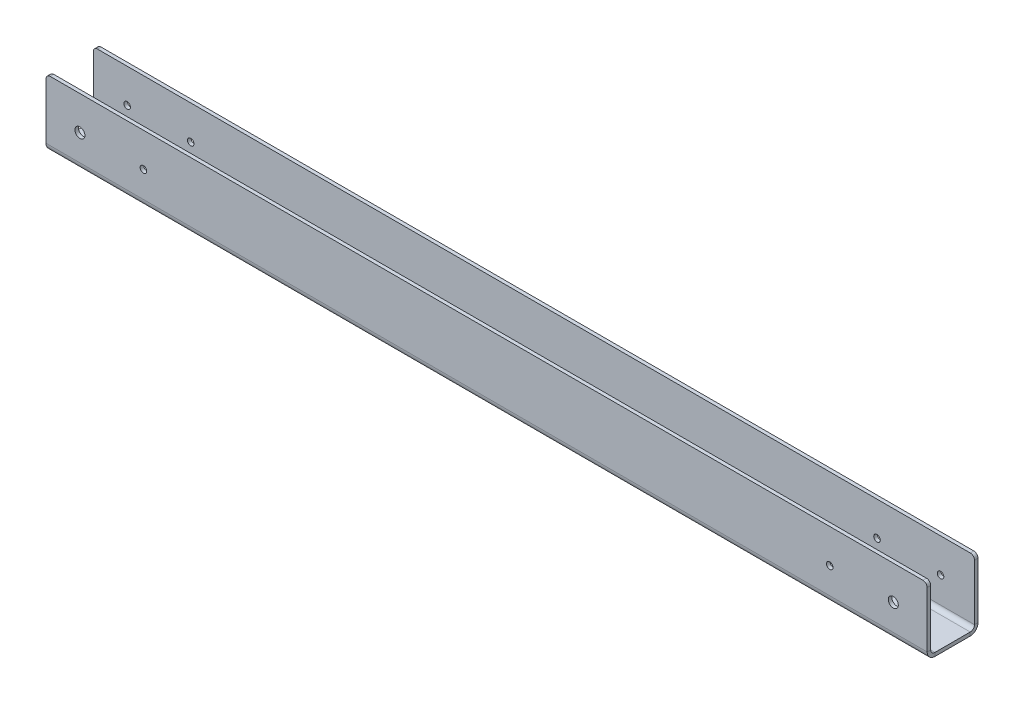
SolidWorks part; units mm, degrees
note: The reader was unsure of these and kept them because the rebuilt part matched: flange length of "Edge-Flange1".
material "Plain Carbon Steel"
ref_plane "Front Plane" through (0, 0, 0) normal (0, 0, 1) x (1, 0, 0)
ref_plane "Top Plane" through (0, 0, 0) normal (0, 1, 0) x (1, 0, 0)
ref_plane "Right Plane" through (0, 0, 0) normal (1, 0, 0) x (0, 0, -1)
sketch "Sketch1" plane through (0, 0, 0) normal (0, 1, 0) x (1, 0, 0)
  line L1 (45.72, -3.175) -> (706.12, -3.175)
  line L3 (45.72, 34.925) -> (706.12, 34.925)
  line L6 (45.72, 34.925) -> (45.72, -3.175)
  line L13 (706.12, 34.925) -> (706.12, -3.175)
  dimension "D1" = 660.4
  dimension "D2" = 38.1
base flange "Base-Flange1" sketch "Sketch1" thickness 2.6568 reverse thickness direction no parameters "D1"=3.175
edge flange "Edge-Flange1" sketch "Sketch10" flange profiles "Sketch10", "Sketch11" flange angle 90 flange length 50.8 flange position material inside bend radius 3.175 thickness 2.6568 relief rectangular parameters "D6"=10, "D8"=1
sketch "Sketch10" plane through (0, 0, 3.175) normal (0, 0, -1) x (-1, 0, 0)
  line L2 (-706.12, 0) -> (-706.12, 48.1432)
  line L3 (-706.12, 48.1432) -> (-45.72, 48.1432)
  line L4 (-45.72, 48.1432) -> (-45.72, 0)
  line L5 (-45.72, 0) -> (-706.12, 0) construction
  line L6 (-45.72, 0) -> (-706.12, 0)
sketch "Sketch11" plane through (0, 0, -34.925) normal (0, 0, 1) x (1, 0, 0)
  line L0 (706.12, 0) -> (45.72, 0) construction
  line L1 (706.12, 0) -> (45.72, 0)
  line L2 (706.12, 0) -> (706.12, 48.1432)
  line L3 (706.12, 48.1432) -> (45.72, 48.1432)
  line L4 (45.72, 48.1432) -> (45.72, 0)
bend "EdgeBend1" bend radius 3.175 bend angle 90 parameters "D5"=1
bend "EdgeBend2" bend radius 3.175 bend angle 90 parameters "D5"=2
edge flange "Edge-Flange2" [suppressed] sketch "Sketch20" flange profiles "Sketch20", "Sketch21", "Sketch22", "Sketch23" flange angle 90 flange position material inside bend radius 3.175 thickness 2.6568
sketch "Sketch20" plane through (0, 0, 0) normal (0, 0, -1) x (-1, 0, 0)
  line L2 (-749.3, 0) -> (-749.3, 48.1432)
  line L3 (-749.3, 48.1432) -> (-704.9084, 48.1432)
  line L4 (-704.9084, 48.1432) -> (-704.9084, 0)
  line L9 (-704.9084, 0) -> (-749.3, 0) construction
  line L10 (-704.9084, 0) -> (-749.3, 0)
sketch "Sketch21" plane through (0, 0, -31.75) normal (0, 0, 1) x (1, 0, 0)
  line L2 (749.3, 0) -> (749.3, 48.1432)
  line L3 (749.3, 48.1432) -> (704.9084, 48.1432)
  line L4 (704.9084, 48.1432) -> (704.9084, 0)
  line L7 (749.3, 0) -> (704.9084, 0) construction
  line L8 (749.3, 0) -> (704.9084, 0)
sketch "Sketch22" plane through (0, 0, -31.75) normal (0, 0, 1) x (1, 0, 0)
  line L0 (44.3916, 0) -> (0, 0) construction
  line L1 (44.3916, 0) -> (0, 0)
  line L2 (44.3916, 0) -> (44.3916, 48.1432)
  line L3 (44.3916, 48.1432) -> (0, 48.1432)
  line L4 (0, 48.1432) -> (0, 0)
sketch "Sketch23" plane through (0, 0, 0) normal (0, 0, -1) x (-1, 0, 0)
  line L0 (0, 0) -> (-44.3916, 0) construction
  line L1 (0, 0) -> (-44.3916, 0)
  line L2 (0, 0) -> (0, 48.1432)
  line L3 (0, 48.1432) -> (-44.3916, 48.1432)
  line L4 (-44.3916, 48.1432) -> (-44.3916, 0)
bend "EdgeBend3" bend radius 3.175 bend angle 90 parameters "D5"=3
bend "EdgeBend4" bend radius 3.175 bend angle 90 parameters "D5"=4
bend "EdgeBend5" bend radius 3.175 bend angle 90 parameters "D5"=5
bend "EdgeBend6" bend radius 3.175 bend angle 90 parameters "D5"=6, "D6"=10, "D7"=50.8
hole_wizard "#10 (0.1935) Diameter Hole1" [suppressed] positions "Sketch24" profile "Sketch25" hole size "#10" standard "ANSI Inch"
sketch "Sketch24" [suppressed] plane through (0, 0, 0) normal (0, 0, 1) x (1, 0, 0)
  line L0 (704.9084, 48.1432) -> (749.3, 48.1432) construction
  line L1 (749.3, 48.1432) -> (749.3, 3.175) construction
  line L2 (0, 3.175) -> (0, 48.1432) construction
  point P0 (739.775, 22.7432)
  point P2 (714.375, 22.7432)
  point P4 (34.925, 22.7432)
  point P6 (9.525, 22.7432)
  dimension "D1" = 25.4
  dimension "D2" = 25.4
  dimension "D3" = 9.525
  dimension "D4" = 25.4
  dimension "D5" = 9.525
sketch "Sketch25" plane through (739.775, 22.7432, 0) normal (1, 0, 0) x (0, -1, 0)
  line L0 (0, 0) -> (0, 34.925)
  line L1 (0, 34.925) -> (2.4574, 34.925)
  line L2 (2.4574, 34.925) -> (2.4574, 0)
  line L5 (2.4574, 0) -> (0, 0)
  line L11 (0, -6.35) -> (0, 107.95) construction
  dimension "Thru Hole Dia." = 4.9149
  dimension "Thru Hole Depth" = 34.925
edge flange "Edge-Flange3" [suppressed] sketch "Sketch28" flange angle 90 flange position material inside bend radius 3.175 thickness 2.6568
sketch "Sketch28" plane through (0, 48.1432, 0.5182) normal (0, 1, 0) x (1, 0, 0)
  line L0 (45.72, 0) -> (703.58, 0) construction
  line L1 (45.72, 0) -> (703.58, 0)
  line L2 (45.72, 0) -> (45.72, 12.7)
  line L3 (45.72, 12.7) -> (703.58, 12.7)
  line L4 (703.58, 12.7) -> (703.58, 0)
  dimension "D1" = 12.7
bend "EdgeBend7" bend radius 3.175 bend angle 90 parameters "D5"=7, "D6"=10, "D7"=15.3568
edge flange "Edge-Flange4" [suppressed] sketch "Sketch31" flange angle 90 flange position material inside bend radius 3.175 thickness 2.6568
sketch "Sketch31" plane through (0, 48.1432, -32.2682) normal (0, -1, 0) x (1, 0, 0)
  line L2 (45.72, 0) -> (45.72, 12.7)
  line L3 (45.72, 12.7) -> (703.58, 12.7)
  line L4 (703.58, 12.7) -> (703.58, 0)
  line L5 (703.58, 0) -> (45.72, 0) construction
  line L6 (703.58, 0) -> (45.72, 0)
  dimension "D1" = 12.7
bend "EdgeBend8" bend radius 3.175 bend angle 90 parameters "D5"=8, "D6"=10, "D7"=15.3568
hole_wizard "#10 (0.1935) Diameter Hole2" positions "Sketch32" profile "Sketch33" hole size "#10" standard "ANSI Inch" end condition up to next
sketch "Sketch32" plane through (0, 0, -34.925) normal (0, 0, -1) x (-1, 0, 0)
  line L0 (-45.72, 3.175) -> (-45.72, 48.1432) construction
  line L1 (-706.12, 48.1432) -> (-706.12, 3.175) construction
  line L2 (-45.72, 48.1432) -> (-706.12, 48.1432) construction
  point P0 (-680.72, 22.7432)
  point P2 (-633.095, 22.7432)
  point P4 (-118.745, 22.7432)
  point P6 (-71.12, 22.7432)
  dimension "D1" = 25.4
  dimension "D2" = 47.625
  dimension "D3" = 25.4
  dimension "D4" = 47.625
  dimension "D5" = 25.4
sketch "Sketch33" plane through (680.72, 22.7432, -34.925) normal (1, 0, 0) x (0, 1, 0)
  line L0 (0, 0) -> (0, 2.6568)
  line L1 (0, 2.6568) -> (2.4574, 2.6568)
  line L2 (2.4574, 2.6568) -> (2.4574, 0)
  line L5 (2.4574, 0) -> (0, 0)
  line L11 (0, -6.35) -> (0, 107.95) construction
  dimension "Thru Hole Dia." = 4.9149
  dimension "Thru Hole Depth" = 2.6568
fillet "Fillet1" radius 3.175 4 edges at (706.12, 48.1432, -33.5966) (706.12, 48.1432, 1.8466) (45.72, 48.1432, -33.5966) (45.72, 48.1432, 1.8466)
hole_wizard "#10 (0.1935) Diameter Hole3" positions "Sketch34" profile "Sketch35" hole size "#10" standard "ANSI Inch" end condition up to next
sketch "Sketch34" plane through (0, 0, 3.175) normal (0, 0, 1) x (1, 0, 0)
  line L0 (45.72, 24.0716) -> (706.12, 24.0716) construction
  line L1 (45.72, 3.175) -> (45.72, 44.9682) construction
  line L2 (706.12, 44.9682) -> (706.12, 3.175) construction
  circle A0 centre (118.745, 22.7432) radius 2.4574 construction
  circle A1 centre (633.095, 22.7432) radius 2.4574 construction
  point P9 (118.745, 22.7432)
  point P15 (633.095, 22.7432)
sketch "Sketch35" plane through (633.095, 22.7432, 3.175) normal (1, 0, 0) x (0, -1, 0)
  line L0 (0, 0) -> (0, 2.6568)
  line L1 (0, 2.6568) -> (2.4574, 2.6568)
  line L2 (2.4574, 2.6568) -> (2.4574, 0)
  line L5 (2.4574, 0) -> (0, 0)
  line L11 (0, -6.35) -> (0, 107.95) construction
  dimension "Thru Hole Dia." = 4.9149
  dimension "Thru Hole Depth" = 2.6568
hole_wizard "19/64 (0.29688) Diameter Hole1" positions "Sketch36" profile "Sketch37" hole size "19/64" standard "ANSI Inch" end condition up to next
sketch "Sketch36" plane through (0, 0, 3.175) normal (0, 0, 1) x (1, 0, 0)
  circle A0 centre (71.12, 22.7432) radius 2.4574 construction
  circle A1 centre (680.72, 22.7432) radius 2.4574 construction
  point P0 (71.12, 22.7432)
  point P5 (680.72, 22.7432)
sketch "Sketch37" plane through (71.12, 22.7432, 3.175) normal (1, 0, 0) x (0, -1, 0)
  line L0 (0, 0) -> (0, 2.6568)
  line L1 (0, 2.6568) -> (3.7704, 2.6568)
  line L2 (3.7704, 2.6568) -> (3.7704, 0)
  line L5 (3.7704, 0) -> (0, 0)
  line L11 (0, -6.35) -> (0, 107.95) construction
  dimension "Thru Hole Dia." = 7.5408
  dimension "Thru Hole Depth" = 2.6568
sketch "Bend-Lines1" [suppressed] plane through (0, 0, 0) normal (0, 1, 0) x (1, 0, 0)
sketch "Bounding-Box1" [suppressed] plane through (0, 0, 0) normal (0, 1, 0) x (1, 0, 0)
sheet metal parameters "Sheet-Metal1" thickness 2.6568 parameters "D1"=3.175
flat pattern "Flat-Pattern1" [suppressed]
sketch "Bend-Lines2" plane through (0, 0, 0) normal (0, 1, 0) x (1, 0, 0)
sketch3d "Bounding-Box2" [suppressed]
  line L0 (749.3, 38.1, 0) -> (0, 38.1, 0) construction
  line L1 (749.3, 0, 0) -> (0, 0, 0) construction
  line L2 (749.3, 38.1, 0) -> (749.3, 0, 0) construction
  line L3 (0, 38.1, 0) -> (0, 0, 0) construction
sheet metal parameters "Sheet-Metal2" thickness 2.6568 parameters "D1"=3.175
flat pattern "Flat-Pattern1"
sketch "Bend-Lines2" plane through (0, 0, 0) normal (0, 1, 0) x (1, 0, 0)
  line L0 (706.12, 32.6301) -> (45.72, 32.6301) construction
  line L1 (45.72, -0.8801) -> (706.12, -0.8801) construction
  line L2 (706.12, 32.6301) -> (45.72, 32.6301) construction
  line L3 (45.72, -0.8801) -> (706.12, -0.8801) construction
sketch3d "Bounding-Box2" [suppressed]
  line L0 (706.12, -49.3853, 0) -> (45.72, -49.3853, 0) construction
  line L1 (706.12, 81.1353, 0) -> (45.72, 81.1353, 0) construction
  line L2 (706.12, -49.3853, 0) -> (706.12, 81.1353, 0) construction
  line L3 (45.72, -49.3853, 0) -> (45.72, 81.1353, 0) construction
bend of the flat pattern "Flatten-<EdgeBend1>1"
bend of the flat pattern "Flatten-<EdgeBend2>1"
sheet metal parameters "Sheet-Metal3" thickness 2.6568 parameters "D1"=3.175
flat pattern "Flat-Pattern1"
sketch "Bend-Lines2" plane through (0, 0, 0) normal (0, 1, 0) x (1, 0, 0)
  line L0 (695.3183, 32.6301) -> (53.975, 32.6301) construction
  line L1 (53.975, -0.8801) -> (695.3183, -0.8801) construction
  line L2 (695.3183, 32.6301) -> (53.975, 32.6301) construction
  line L3 (53.975, -0.8801) -> (695.3183, -0.8801) construction
  line L4 (0, 2.2949) -> (52.6466, 2.2949) construction
  line L5 (0, 29.4551) -> (52.6466, 29.4551) construction
  line L6 (696.6467, 29.4551) -> (749.2933, 29.4551) construction
  line L7 (749.2933, 2.2949) -> (696.6467, 2.2949) construction
  line L8 (0, 2.2949) -> (52.6466, 2.2949) construction
  line L9 (0, 29.4551) -> (52.6466, 29.4551) construction
  line L10 (696.6467, 29.4551) -> (749.2933, 29.4551) construction
  line L11 (749.2933, 2.2949) -> (696.6467, 2.2949) construction
sketch3d "Bounding-Box2" [suppressed]
  line L0 (749.2933, 81.1353, 0) -> (0, 81.1353, 0) construction
  line L1 (749.2933, -49.3853, 0) -> (0, -49.3853, 0) construction
  line L2 (749.2933, 81.1353, 0) -> (749.2933, -49.3853, 0) construction
  line L3 (0, 81.1353, 0) -> (0, -49.3853, 0) construction
bend of the flat pattern "Flatten-<EdgeBend1>1"
bend of the flat pattern "Flatten-<EdgeBend2>1"
bend of the flat pattern "Flatten-<EdgeBend3>1"
bend of the flat pattern "Flatten-<EdgeBend4>1"
bend of the flat pattern "Flatten-<EdgeBend5>1"
bend of the flat pattern "Flatten-<EdgeBend6>1"
sheet metal parameters "Sheet-Metal4" thickness 2.6568 parameters "D1"=3.175
flat pattern "Flat-Pattern1"
sketch "Bend-Lines2" plane through (0, 0, 0) normal (0, 1, 0) x (1, 0, 0)
  line L0 (703.58, 32.6301) -> (45.72, 32.6301) construction
  line L1 (45.72, -0.8801) -> (703.58, -0.8801) construction
  line L2 (703.58, 32.6301) -> (45.72, 32.6301) construction
  line L3 (45.72, -0.8801) -> (703.58, -0.8801) construction
  line L4 (44.3916, 2.2949) -> (0, 2.2949) construction
  line L5 (0, 29.4551) -> (44.3916, 29.4551) construction
  line L6 (749.3, 29.4551) -> (704.9084, 29.4551) construction
  line L7 (749.3, 2.2949) -> (704.9084, 2.2949) construction
  line L8 (44.3916, 2.2949) -> (0, 2.2949) construction
  line L9 (0, 29.4551) -> (44.3916, 29.4551) construction
  line L10 (749.3, 29.4551) -> (704.9084, 29.4551) construction
  line L11 (749.3, 2.2949) -> (704.9084, 2.2949) construction
sketch3d "Bounding-Box2" [suppressed]
  line L0 (749.3, 81.1353, 0) -> (0, 81.1353, 0) construction
  line L1 (749.3, -49.3853, 0) -> (0, -49.3853, 0) construction
  line L2 (749.3, 81.1353, 0) -> (749.3, -49.3853, 0) construction
  line L3 (0, 81.1353, 0) -> (0, -49.3853, 0) construction
bend of the flat pattern "Flatten-<EdgeBend1>1"
bend of the flat pattern "Flatten-<EdgeBend2>1"
bend of the flat pattern "Flatten-<EdgeBend3>1"
bend of the flat pattern "Flatten-<EdgeBend4>1"
bend of the flat pattern "Flatten-<EdgeBend5>1"
bend of the flat pattern "Flatten-<EdgeBend6>1"
sheet metal parameters "Sheet-Metal5" thickness 2.6568 parameters "D1"=3.175
flat pattern "Flat-Pattern1"
sketch "Bend-Lines2" plane through (0, 0, 0) normal (0, 1, 0) x (1, 0, 0)
  line L0 (703.58, 32.6301) -> (45.72, 32.6301) construction
  line L1 (45.72, -0.8801) -> (703.58, -0.8801) construction
  line L2 (703.58, 32.6301) -> (45.72, 32.6301) construction
  line L3 (45.72, -0.8801) -> (703.58, -0.8801) construction
  line L4 (44.3916, 2.2949) -> (0, 2.2949) construction
  line L5 (0, 29.4551) -> (44.3916, 29.4551) construction
  line L6 (749.3, 29.4551) -> (704.9084, 29.4551) construction
  line L7 (749.3, 2.2949) -> (704.9084, 2.2949) construction
  line L8 (44.3916, 2.2949) -> (0, 2.2949) construction
  line L9 (0, 29.4551) -> (44.3916, 29.4551) construction
  line L10 (749.3, 29.4551) -> (704.9084, 29.4551) construction
  line L11 (749.3, 2.2949) -> (704.9084, 2.2949) construction
  line L12 (45.72, -47.0904) -> (703.58, -47.0904) construction
  line L13 (45.72, -47.0904) -> (703.58, -47.0904) construction
sketch3d "Bounding-Box2" [suppressed]
  line L0 (749.3, 81.1353, 0) -> (0, 81.1353, 0) construction
  line L1 (749.3, -63.8456, 0) -> (0, -63.8456, 0) construction
  line L2 (749.3, 81.1353, 0) -> (749.3, -63.8456, 0) construction
  line L3 (0, 81.1353, 0) -> (0, -63.8456, 0) construction
bend of the flat pattern "Flatten-<EdgeBend1>1"
bend of the flat pattern "Flatten-<EdgeBend2>1"
bend of the flat pattern "Flatten-<EdgeBend3>1"
bend of the flat pattern "Flatten-<EdgeBend4>1"
bend of the flat pattern "Flatten-<EdgeBend5>1"
bend of the flat pattern "Flatten-<EdgeBend6>1"
bend of the flat pattern "Flatten-<EdgeBend7>1"
sheet metal parameters "Sheet-Metal6" thickness 2.6568 parameters "D1"=3.175
flat pattern "Flat-Pattern1"
sketch "Bend-Lines2" plane through (0, 0, 0) normal (0, 1, 0) x (1, 0, 0)
  line L0 (703.58, 32.6301) -> (45.72, 32.6301) construction
  line L1 (45.72, -0.8801) -> (703.58, -0.8801) construction
  line L2 (703.58, 32.6301) -> (45.72, 32.6301) construction
  line L3 (45.72, -0.8801) -> (703.58, -0.8801) construction
  line L4 (44.3916, 2.2949) -> (0, 2.2949) construction
  line L5 (0, 29.4551) -> (44.3916, 29.4551) construction
  line L6 (749.3, 29.4551) -> (704.9084, 29.4551) construction
  line L7 (749.3, 2.2949) -> (704.9084, 2.2949) construction
  line L8 (44.3916, 2.2949) -> (0, 2.2949) construction
  line L9 (0, 29.4551) -> (44.3916, 29.4551) construction
  line L10 (749.3, 29.4551) -> (704.9084, 29.4551) construction
  line L11 (749.3, 2.2949) -> (704.9084, 2.2949) construction
  line L12 (45.72, -47.0904) -> (703.58, -47.0904) construction
  line L13 (45.72, -47.0904) -> (703.58, -47.0904) construction
  line L14 (703.58, 78.8404) -> (45.72, 78.8404) construction
  line L15 (703.58, 78.8404) -> (45.72, 78.8404) construction
sketch3d "Bounding-Box2" [suppressed]
  line L0 (749.3, 91.9024, 0) -> (0, 91.9024, 0) construction
  line L1 (749.3, -60.1524, 0) -> (0, -60.1524, 0) construction
  line L2 (749.3, 91.9024, 0) -> (749.3, -60.1524, 0) construction
  line L3 (0, 91.9024, 0) -> (0, -60.1524, 0) construction
bend of the flat pattern "Flatten-<EdgeBend1>1"
bend of the flat pattern "Flatten-<EdgeBend2>1"
bend of the flat pattern "Flatten-<EdgeBend3>1"
bend of the flat pattern "Flatten-<EdgeBend4>1"
bend of the flat pattern "Flatten-<EdgeBend5>1"
bend of the flat pattern "Flatten-<EdgeBend6>1"
bend of the flat pattern "Flatten-<EdgeBend7>1"
bend of the flat pattern "Flatten-<EdgeBend8>1"
sheet metal parameters "Sheet-Metal8" thickness 2.6568 parameters "D1"=3.175
flat pattern "Flat-Pattern1"
sketch "Bend-Lines2" plane through (0, 0, 0) normal (0, 1, 0) x (1, 0, 0)
  line L0 (706.12, 32.6301) -> (45.72, 32.6301) construction
  line L1 (45.72, -0.8801) -> (706.12, -0.8801) construction
  line L2 (706.12, 32.6301) -> (45.72, 32.6301) construction
  line L3 (45.72, -0.8801) -> (706.12, -0.8801) construction
sketch3d "Bounding-Box2" [suppressed]
  line L0 (45.72, -49.3844, 0) -> (706.12, -49.3853, 0) construction
  line L1 (45.7202, 81.1353, 0) -> (706.1202, 81.1344, 0) construction
  line L2 (45.72, -49.3844, 0) -> (45.7202, 81.1353, 0) construction
  line L3 (706.12, -49.3853, 0) -> (706.1202, 81.1344, 0) construction
bend of the flat pattern "Flatten-<EdgeBend1>1"
bend of the flat pattern "Flatten-<EdgeBend2>1"
sheet metal parameters "Sheet-Metal9" thickness 2.6568 parameters "D1"=3.175
flat pattern "Flat-Pattern1"
sketch "Bend-Lines2" plane through (0, 0, 0) normal (0, 1, 0) x (1, 0, 0)
  line L0 (706.12, 32.6301) -> (45.72, 32.6301) construction
  line L1 (45.72, -0.8801) -> (706.12, -0.8801) construction
  line L2 (706.12, 32.6301) -> (45.72, 32.6301) construction
  line L3 (45.72, -0.8801) -> (706.12, -0.8801) construction
sketch3d "Bounding-Box2" [suppressed]
  line L0 (45.72, -49.3844, 0) -> (706.12, -49.3853, 0) construction
  line L1 (45.7202, 81.1353, 0) -> (706.1202, 81.1344, 0) construction
  line L2 (45.72, -49.3844, 0) -> (45.7202, 81.1353, 0) construction
  line L3 (706.12, -49.3853, 0) -> (706.1202, 81.1344, 0) construction
bend of the flat pattern "Flatten-<EdgeBend1>1"
bend of the flat pattern "Flatten-<EdgeBend2>1"
sheet metal parameters "Sheet-Metal10" thickness 2.6568 parameters "D1"=3.175
flat pattern "Flat-Pattern1"
sketch "Bend-Lines2" plane through (0, 0, 0) normal (0, 1, 0) x (1, 0, 0)
  line L0 (706.12, 32.6301) -> (45.72, 32.6301) construction
  line L1 (45.72, -0.8801) -> (706.12, -0.8801) construction
  line L2 (706.12, 32.6301) -> (45.72, 32.6301) construction
  line L3 (45.72, -0.8801) -> (706.12, -0.8801) construction
sketch3d "Bounding-Box2" [suppressed]
  line L0 (45.72, -49.3844, 0) -> (706.12, -49.3853, 0) construction
  line L1 (45.7202, 81.1353, 0) -> (706.1202, 81.1344, 0) construction
  line L2 (45.72, -49.3844, 0) -> (45.7202, 81.1353, 0) construction
  line L3 (706.12, -49.3853, 0) -> (706.1202, 81.1344, 0) construction
bend of the flat pattern "Flatten-<EdgeBend1>1"
bend of the flat pattern "Flatten-<EdgeBend2>1"
